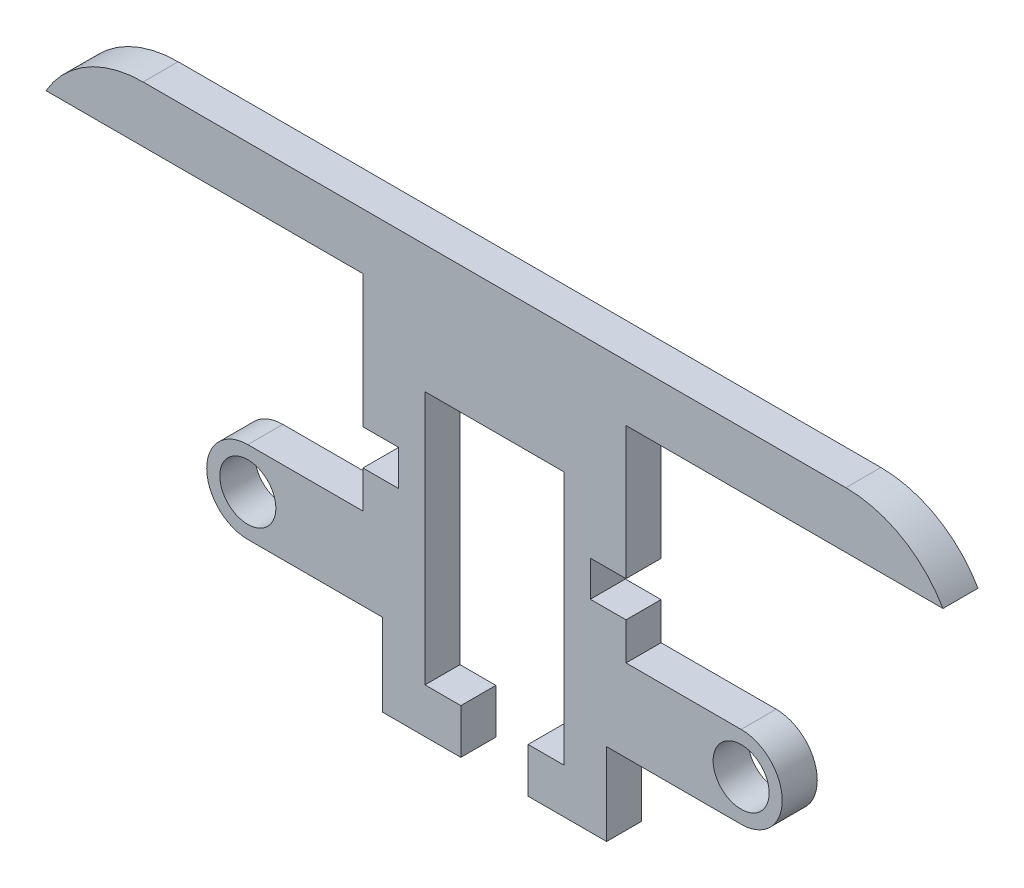
SolidWorks part; units mm, degrees
ref_plane "Front Plane" through (0, 0, 0) normal (0, 0, 1) x (1, 0, 0)
ref_plane "Top Plane" through (0, 0, 0) normal (0, 1, 0) x (1, 0, 0)
ref_plane "Right Plane" through (0, 0, 0) normal (1, 0, 0) x (0, 0, -1)
sketch "Sketch1" plane through (0, 0, 0) normal (0, 0, 1) x (1, 0, 0)
  line L22 (0, 19) -> (40, 19)
  line L23 (0, 19) -> (40, 19) construction
  line L24 (0, 19) -> (0, -19) construction
  line L25 (0, -19) -> (40, -19) construction
  line L26 (40, 19) -> (40, -19) construction
  line L27 (40, 19) -> (40, 14)
  line L28 (40, 14) -> (11.73, 14)
  line L29 (11.73, 14) -> (11.73, 2.17)
  line L30 (11.73, 2.17) -> (8.55, 2.17)
  line L31 (8.55, 2.17) -> (8.55, -1.01)
  line L32 (8.55, -1.01) -> (11.73, -1.01)
  line L33 (11.73, -1.01) -> (11.73, -4.34)
  line L34 (11.73, -4.34) -> (22, -4.34)
  line L35 (22, -4.34) -> (22, -11.67) construction
  line L36 (22, -11.67) -> (10, -11.67)
  line L37 (10, -11.67) -> (10, -19)
  line L38 (10, -19) -> (3, -19)
  line L39 (3, -19) -> (3, -15)
  line L40 (3, -15) -> (6.2, -15)
  line L41 (6.2, -15) -> (6.2, 7.65)
  line L42 (6.2, 7.65) -> (0, 7.65)
  line L43 (0, 19) -> (0, 7.65)
  arc A0 (22, -11.67) -> (22, -4.34) centre (22, -8.005) ccw
  circle A1 centre (22, -8.005) radius 2.5
  point P0 (11.9845, 12.9257)
  point P5 (0, 0)
  dimension "D16" = 5
  dimension "D1" = 40
  dimension "D2" = 38
  dimension "D3" = 6.2
  dimension "D4" = 11.35
  dimension "D5" = 5
  dimension "D6" = 11.83
  dimension "D7" = 28.27
  dimension "D8" = 3.18
  dimension "D9" = 3.18
  dimension "D10" = 3.33
  dimension "D11" = 10.27
  dimension "D12" = 7.33
  dimension "D13" = 7
  dimension "D14" = 3
  dimension "D15" = 4
extrude "Boss-Extrude1" add sketch "Sketch1" along normal blind 3.125
mirror "Mirror1" about plane through (0, 19, 3.125) normal (1, 0, 0) of "Boss-Extrude1"
fillet "Fillet1" radius 10 2 edges at (-40, 19, 1.5625) (40, 19, 1.5625)
